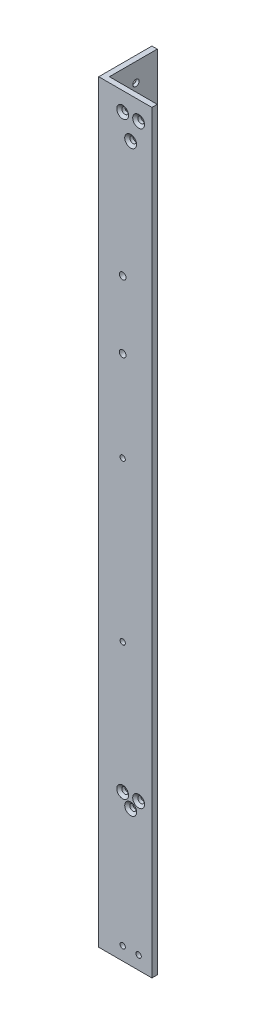
SolidWorks part; units mm, degrees
ref_plane "Front Plane" through (0, 0, 0) normal (0, 0, 1) x (1, 0, 0)
ref_plane "Top Plane" through (0, 0, 0) normal (0, 1, 0) x (1, 0, 0)
ref_plane "Right Plane" through (0, 0, 0) normal (1, 0, 0) x (0, 0, -1)
sketch "Sketch2" plane through (0, 0, 0) normal (0, 1, 0) x (1, 0, 0)
  line L0 (0, 31.75) -> (3.175, 31.75)
  line L1 (3.175, 31.75) -> (3.175, 3.175)
  line L2 (3.175, 3.175) -> (31.75, 3.175)
  line L3 (31.75, 3.175) -> (31.75, 0)
  line L4 (31.75, 0) -> (0, 0)
  line L5 (0, 0) -> (0, 31.75)
  point P9 (1.5875, 31.75)
  point P10 (31.75, 1.5875)
  dimension "D4" = 3.175
  dimension "D1" = 31.75
  dimension "D2" = 31.75
  dimension "D3" = 3.175
extrude "Boss-Extrude1" add sketch "Sketch2" along normal blind 450
sketch "FrontSideHoles-Sketch3" plane through (0, 0, 0) normal (0, 0, 1) x (1, 0, 0)
  line L0 (0, 0) -> (31.75, 0) construction
  line L1 (0, 450) -> (0, 0) construction
  circle A1 centre (19.05, 81.1125) radius 1.5875
  circle A2 centre (14.2875, 87.4625) radius 1.5875
  circle A3 centre (23.8125, 87.4625) radius 1.5875
  circle A4 centre (14.2875, 438.8875) radius 1.5875
  circle A6 centre (23.8125, 438.8875) radius 1.5875
  circle A7 centre (19.05, 426.1875) radius 1.5875
  circle A8 centre (14.2875, 354.1849) radius 2
  circle A9 centre (14.2875, 313.9849) radius 2
  circle A10 centre (14.2875, 260) radius 1.5875
  circle A11 centre (14.2875, 165) radius 1.5875
  circle A13 centre (14.2875, 7.9375) radius 1.5875
  circle A14 centre (23.8125, 7.9375) radius 1.5875
  point P0 (23.8125, 81.1125)
  dimension "D4" = 3.175
  dimension "D15" = 4
  dimension "D13" = 3.175
  dimension "D8" = 11.1125
  dimension "D11" = 40.2
  dimension "D6" = 165
  dimension "D10" = 95
  dimension "D12" = 7.9375
  dimension "D2" = 14.2875
  dimension "D5" = 6.35
  dimension "D14" = 81.1125
  dimension "D7" = 12.7
  dimension "D16" = 14.2875
  dimension "D9" = 354.1849
  dimension "D3" = 9.525
  dimension "D17" = 19.05
sketch "LeftSideHoles-Sketch4" plane through (0, 0, 0) normal (-1, 0, 0) x (0, 0, 1)
  line L0 (-31.75, 450) -> (0, 450) construction
  line L1 (0, 450) -> (0, 0) construction
  line L3 (-31.75, 0) -> (0, 0) construction
  circle A0 centre (-23.8125, 81.1125) radius 1.5875
  circle A1 centre (-14.2875, 81.1125) radius 1.5875
  circle A2 centre (-19.05, 87.4625) radius 1.5875
  circle A4 centre (-19.05, 438.8875) radius 1.5875
  circle A6 centre (-23.8125, 426.1875) radius 1.5875
  circle A7 centre (-14.2875, 426.1875) radius 1.5875
  circle A8 centre (-23.8125, 341.2474) radius 1.5875
  circle A9 centre (-14.2875, 341.2474) radius 1.5875
  circle A10 centre (-23.8125, 306.3224) radius 1.5875
  circle A11 centre (-14.2875, 306.3224) radius 1.5875
  circle A12 centre (-23.8125, 7.9375) radius 1.5875
  circle A13 centre (-14.2875, 7.9375) radius 1.5875
  circle A14 centre (-14.2875, 165) radius 1.5875
  circle A15 centre (-14.2875, 260) radius 1.5875
  circle A16 centre (-14.2875, 355) radius 1.5875
  point P14 (-17.1858, 87.4625)
  point P15 (-27.8787, 87.4625)
  dimension "D4" = 3.175
  dimension "D2" = 14.2875
  dimension "D5" = 6.35
  dimension "D7" = 12.7
  dimension "D3" = 81.1125
  dimension "D6" = 11.1125
  dimension "D10" = 7.9375
  dimension "D9" = 34.925
  dimension "D11" = 9.525
  dimension "D8" = 341.2474
  dimension "D12" = 165
  dimension "D13" = 95
  dimension "D14" = 95
  dimension "D15" = 19.05
extrude "FrontSideHoles-Cut-Extrude1" cut sketch "FrontSideHoles-Sketch3" against normal blind 3.175
extrude "LeftSideHoles-Cut-Extrude2" cut sketch "LeftSideHoles-Sketch4" against normal blind 3.175
sketch "Sketch3" plane through (0, 0, 0) normal (0, 0, 1) x (1, 0, 0)
  point P0 (14.2875, 87.4625)
  point P3 (19.05, 81.1125)
  point P6 (23.8125, 87.4625)
  point P9 (19.05, 426.1875)
  point P12 (14.2875, 438.8875)
  point P15 (23.8125, 438.8875)
hole_wizard "CSK for #6 Flat Head Machine Screw (100)1" positions "Sketch3" profile "Sketch4" countersink size "#6" standard "ANSI Inch" end condition through all
sketch "Sketch4" plane through (14.2875, 87.4625, 0) normal (1, 0, 0) x (0, -1, 0)
  line L0 (0, 0) -> (0, 31.75)
  line L1 (0, 31.75) -> (1.8986, 31.75)
  line L2 (1.8986, 31.75) -> (1.8986, 1.38)
  line L3 (1.8986, 1.38) -> (3.5433, 0)
  line L5 (3.5433, 0) -> (0, 0)
  line L6 (-1.8986, 1.38) -> (-3.5433, 0) construction
  line L11 (0, -6.35) -> (0, 107.95) construction
  dimension "Thru Hole Dia." = 3.7973
  dimension "Thru Hole Depth" = 31.75
  dimension "Near C'Sink Dia." = 7.0866
  dimension "Near C'Sink Angle" = 100
sketch "Sketch8" plane through (0, 0, 0) normal (-1, 0, 0) x (0, 0, 1)
  point P0 (-19.05, 87.4625)
  point P3 (-23.8125, 81.1125)
  point P6 (-14.2875, 81.1125)
  point P9 (-23.8125, 341.2474)
  point P12 (-14.2875, 341.2474)
  point P15 (-14.2875, 306.3224)
  point P18 (-23.8125, 306.3224)
  point P21 (-23.8125, 426.1875)
  point P24 (-14.2875, 426.1875)
  point P27 (-19.05, 438.8875)
hole_wizard "CSK for #6 Flat Head Machine Screw (100)2" positions "Sketch8" profile "Sketch9" countersink size "#6" standard "ANSI Inch" end condition through all
sketch "Sketch9" plane through (0, 87.4625, -19.05) normal (0, 1, 0) x (0, 0, 1)
  line L0 (0, 0) -> (0, 31.75)
  line L1 (0, 31.75) -> (1.8986, 31.75)
  line L2 (1.8986, 31.75) -> (1.8986, 1.38)
  line L3 (1.8986, 1.38) -> (3.5433, 0)
  line L5 (3.5433, 0) -> (0, 0)
  line L6 (-1.8986, 1.38) -> (-3.5433, 0) construction
  line L11 (0, -6.35) -> (0, 107.95) construction
  dimension "Thru Hole Dia." = 3.7973
  dimension "Thru Hole Depth" = 31.75
  dimension "Near C'Sink Dia." = 7.0866
  dimension "Near C'Sink Angle" = 100
equation "\"RailThickness\"= .125in'Spec"
equation "\"VSWidth\"= 1.25in'Spec"
equation "\"VSHeight\"= 1.25in'Spec"
equation "\"VSLength\"= 450mm"
equation "\"HoleOffsetFromEdge\"= \"RailThickness\" * 2.5"
equation "\"HoleOffsetFromSide\"= \"RailThickness\" * 3.5"
equation "\"LegHeight\"= 70mm'Space needed for PSU/Stepper/Electronics"
equation "\"VSBottomSideRailHoleY1FromBottomOfLowerRail\"= \"V1 BottomOfLowerRail\" + \"HoleOffsetFromSide\"'Equals 81.1125"
equation "\"VSSideRailHoleX1FromSide\"= \"HoleOffsetFromSide\" + \"RailThickness\""
equation "\"FasteningHoleDiameter\"= .125in"
equation "\"VSBottomSideRailHoleY2FromY1\"= \"LowerRailHeight\" - \"HoleOffsetFromSide\" - \"HoleOffsetFromEdge\"'Equals 6.35"
equation "\"VSTopSideRailHoleY1FromEdge\"= \"HoleOffsetFromEdge\" + \"RailThickness\""
equation "\"D4@FrontSideHoles-Sketch3\" = \"FasteningHoleDiameter\""
equation "\"D1@Boss-Extrude1\"=\"VSLength\""
equation "\"D4@LeftSideHoles-Sketch4\" = \"FasteningHoleDiameter\""
equation "\"D3@LeftSideHoles-Sketch4\"= \"VSBottomSideRailHoleY1FromBottomOfLowerRail\""
equation "\"D8@FrontSideHoles-Sketch3\" = \"VSTopSideRailHoleY1FromEdge\""
equation "\"D6@LeftSideHoles-Sketch4\" = \"VSTopSideRailHoleY1FromEdge\""
equation "\"VSMidSideRailHoleY1FromV8TopOfMidSideRail\"= \"V8 ToTopOfMidSideRail\" - \"HoleOffsetFromEdge\"'Equals 341.24737"
equation "\"LowerRailHeight\"= 1.00in"
equation "\"D1@Sketch2\"=\"VSHeight\""
equation "\"D2@Sketch2\"=\"VSWidth\""
equation "\"TopRailHeight\"= 1.25in"
equation "\"MidLeftOrRightSideRailHeight\"= 2.0in"
equation "\"D10@LeftSideHoles-Sketch4\"=\"HoleOffsetFromEdge\""
equation "\"VSMidSideRailHoleY2FromY1\"= \"MidLeftOrRightSideRailHeight\" - \"HoleOffsetFromEdge\" * 2'Equals 34.925"
equation "\"D9@LeftSideHoles-Sketch4\"=\"VSMidSideRailHoleY2FromY1\""
equation "\"VSSideRailHoleX2FromX1\"= \"VSWidth\" - \"VSSideRailHoleX1FromSide\" - \"HoleOffsetFromEdge\""
equation "\"D11@LeftSideHoles-Sketch4\"=\"VSSideRailHoleX2FromX1\""
equation "\"VSTopSideRailHoleY2FromY1\"= \"TopRailHeight\" - \"VSTopSideRailHoleY1FromEdge\" - \"HoleOffsetFromEdge\"'Equals 12.7"
equation "\"D7@LeftSideHoles-Sketch4\"=\"VSTopSideRailHoleY2FromY1\""
equation "\"BeltTensionerInnerHeight\"= \"20TGT2PulleyWidth\" * 2 + \"1mmSpacer\" * 3"
equation "\"20TGT2PulleyWidth\"= 8.7mm'The STL of the Pulley in the diagram is a bit larger"
equation "\"1mmSpacer\"= 1mm"
equation "\"BeltTensionerHeight\"= 60mm"
equation "\"D11@FrontSideHoles-Sketch3\"=\"VSBeltTensionerHoleY2FromY1\""
equation "\"VSBeltTensionerHoleY1ToAlignWithYAxisGantryBlockUpperPulley\"= \"V5 ToBottomOfXAxisLinearRail\" - \"DistanceFromXAxisLinearRailBottomAndTopGantryPulley\" + \"DistanceFromBeltTensionerTopPulleyToBeltTensionertop\" - \"BeltTensionerMountingHoleOffsetFromTopOrBottom\"'Equals 354.18487"
equation "\"VSBeltTensionerHoleY2FromY1\"= \"BeltTensionerHeight\" - \"BeltTensionerMountingHoleOffsetFromTopOrBottom\" * 2"
equation "\"V1 BottomOfLowerRail\"= \"LegHeight\""
equation "\"StepperShaftLength\"= 24mm'Pulley will be attached to the end"
equation "\"ZAxisLeadScrewLength\"= 200mm"
equation "\"LM8UUHeight\"= 24mm'Spec"
equation "\"V2 ToBedAtTopOfZAxis\"= \"V1 BottomOfLowerRail\" - \"LowerEnclosureThickness\" + \"StepperShaftLength\" + \"ZAxisLeadScrewLength\" - \"LM8UUHeight\" / 2'Equals 277"
equation "\"HotEndToTopOfXAxisGB\"= 71.68487mm'Equals 71.68487. Measured after installed onto X-Axis linear rail guide block"
equation "\"TopOfGBToBottomOfLinearRail\"= \"LinearGBWidth\" / 2 + \"LinearRailWidth\" / 2'Equals 19.5"
equation "\"LinearGBWidth\"= 27mm'Spec"
equation "\"V5 ToBottomOfXAxisLinearRail\"= \"V4 ToTopOfBuildPlate/HotEndTip\" + \"HotEndToTopOfXAxisGB\" - \"TopOfGBToBottomOfLinearRail\"'Equals 352.18487"
equation "\"LinearRailWidth\"= 12mm'Spec"
equation "\"V6 ToMiddleOfYAxisGantryBlock\"= \"V5 ToBottomOfXAxisLinearRail\" - \"GABHeight\" / 2'Equals 334.18487"
equation "\"GABUpperHeight\"= 4mm"
equation "\"GABMidWallHeight\"= 28mm'Must equal 28 or changes alignment"
equation "\"D8@LeftSideHoles-Sketch4\"= \"VSMidSideRailHoleY1FromV8TopOfMidSideRail\""
equation "\"BedToBuildPlateStandoffLength\"= 15mm"
equation "\"BuildPlateHeight\"= 8mm'Spec"
equation "\"V4 ToTopOfBuildPlate/HotEndTip\"= \"V2 ToBedAtTopOfZAxis\" + \"BedToBuildPlateStandoffLength\" + \"BuildPlateHeight\""
equation "\"V8 ToTopOfMidSideRail\"= \"V6 ToMiddleOfYAxisGantryBlock\" + \"MidSideRailVerticalOffset\"'Equals 349.18487"
equation "\"VSEnclosureOffsets\"= ( \"VSLength\" - \"LegHeight\" ) / 4"
equation "\"D6@FrontSideHoles-Sketch3\"=\"LegHeight\" + \"VSEnclosureOffsets\""
equation "\"D10@FrontSideHoles-Sketch3\"=\"VSEnclosureOffsets\""
equation "\"D12@FrontSideHoles-Sketch3\"=\"HoleOffsetFromEdge\""
equation "\"D13@LeftSideHoles-Sketch4\"=\"VSEnclosureOffsets\""
equation "\"D12@LeftSideHoles-Sketch4\"=\"LegHeight\" + \"VSEnclosureOffsets\""
equation "\"D2@FrontSideHoles-Sketch3\"=\"VSSideRailHoleX1FromSide\""
equation "\"D5@FrontSideHoles-Sketch3\"=\"VSBottomSideRailHoleY2FromY1\""
equation "\"D14@FrontSideHoles-Sketch3\"=\"VSBottomSideRailHoleY1FromBottomOfLowerRail\""
equation "\"D7@FrontSideHoles-Sketch3\"=\"VSTopSideRailHoleY2FromY1\""
equation "\"D5@LeftSideHoles-Sketch4\"=\"VSBottomSideRailHoleY2FromY1\""
equation "\"BeltTensionerMountingHoleDiameter\"= 4.0mm"
equation "\"D15@FrontSideHoles-Sketch3\"=\"BeltTensionerMountingHoleDiameter\""
equation "\"LowerEnclosureThickness\"= 5mm"
equation "\"GABLowerHeight\"= 4mm"
equation "\"GABHeight\"= \"GABLowerHeight\" + \"GABMidWallHeight\" + \"GABUpperHeight\""
equation "\"D14@LeftSideHoles-Sketch4\"=\"VSEnclosureOffsets\""
equation "\"BeltTensionerMountingHoleOffsetFromTopOrBottom\"= ( \"BeltTensionerHeight\" - \"BeltTensionerInnerHeight\" ) / 4"
equation "\"D13@FrontSideHoles-Sketch3\"=\"FasteningHoleDiameter\""
equation "\"VSBeltTensionerXMountingHoleOffsetFromSide\"= \"BeltTensionerMountingHoleOffsetFromEdge\" + \"RailThickness\" * 2"
equation "\"BeltTensionerMountingHoleOffsetFromEdge\"= \"HoleOffsetFromEdge\""
equation "\"D16@FrontSideHoles-Sketch3\"=\"VSBeltTensionerXMountingHoleOffsetFromSide\""
equation "\"MidSideRailVerticalOffset\"= \"LinearRailWidth\" + 3mm'Allows space for RodStabilizer to attach to bottom of MidSideRail"
equation "\"GABRiserBossOffset\"= 0.4mm'Aligns Pulleys inside edges to be 2.5mm (.5mm apart top to bottom)"
equation "\"GABMidShortRiserHeight\"= \"GABMidWallHeight\" / 2 - \"20TGT2PulleyWidth\"'Equals 5.3"
equation "\"7mmx1mmSpacerHeight\"= 1mm"
equation "\"D9@FrontSideHoles-Sketch3\"=\"VSBeltTensionerHoleY1ToAlignWithYAxisGantryBlockUpperPulley\""
equation "\"DistanceFromXAxisLinearRailBottomAndTopGantryPulley\"= \"GABUpperHeight\" + \"GABMidShortRiserHeight\" - \"GABRiserBossOffset\"'Equals 8.9"
equation "\"DistanceFromBeltTensionerTopPulleyToBeltTensionertop\"= \"7mmx1mmSpacerHeight\" + \"BeltTensionerTopHeight\"'Equals 20.8"
equation "\"BeltTensionerTopHeight\"= ( \"BeltTensionerHeight\" - \"BeltTensionerInnerHeight\" ) / 2'Equals 19.8"
equation "\"VSMidSideRailHoleXFromSideToCenter\"= \"RailThickness\" * 6"
equation "\"D3@FrontSideHoles-Sketch3\"=\"VSSideRailHoleX2FromX1\""
equation "\"D17@FrontSideHoles-Sketch3\"=\"VSMidSideRailHoleXFromSideToCenter\""
equation "\"D2@LeftSideHoles-Sketch4\"=\"VSSideRailHoleX1FromSide\""
